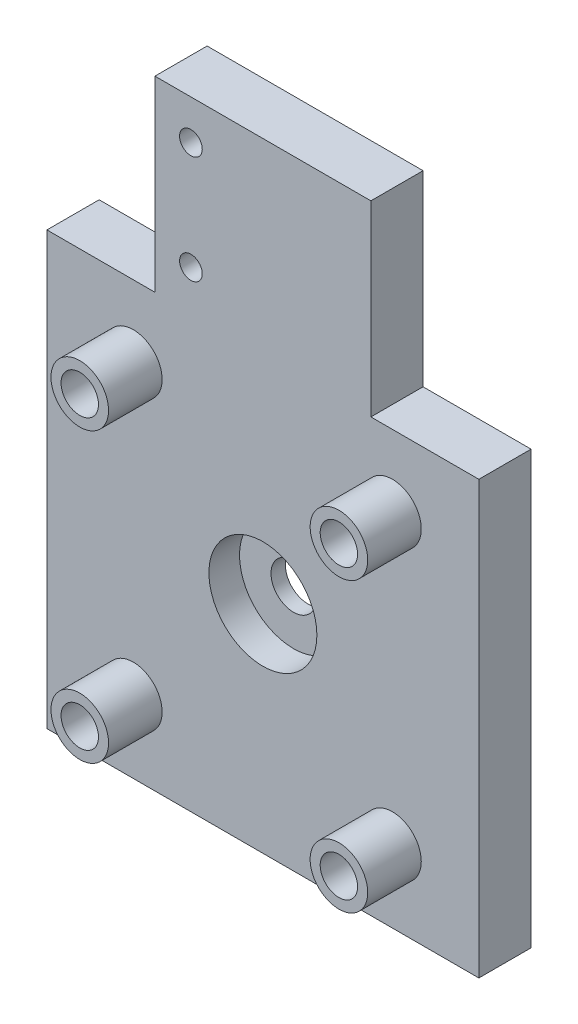
SolidWorks part; units mm, degrees
ref_plane "Front Plane" through (0, 0, 0) normal (0, 0, 1) x (1, 0, 0)
ref_plane "Top Plane" through (0, 0, 0) normal (0, 1, 0) x (1, 0, 0)
ref_plane "Right Plane" through (0, 0, 0) normal (1, 0, 0) x (0, 0, -1)
sketch "Sketch1" plane through (0, 0, 0) normal (0, 0, 1) x (1, 0, 0)
  line L1 (-19.05, -38.1) -> (19.05, -38.1)
  line L2 (-19.05, -38.1) -> (-19.05, 38.1)
  line L3 (-19.05, 38.1) -> (19.05, 38.1)
  line L4 (19.05, -38.1) -> (19.05, 38.1)
  line L5 (-19.05, -38.1) -> (19.05, 38.1) construction
  line L6 (-19.05, 38.1) -> (19.05, -38.1) construction
  point P0 (0, 0)
  dimension "D1" = 38.1
  dimension "D2" = 76.2
extrude "Boss-Extrude1" add sketch "Sketch1" along normal blind 7.9375
sketch "Sketch2" plane through (0, 0, 7.9375) normal (0, 0, 1) x (1, 0, 0)
  circle A0 centre (0, 0) radius 3.9688
  dimension "D1" = 7.9375
extrude "Cut-Extrude1" cut sketch "Sketch2" against normal through all
sketch "Sketch4" plane through (0, 0, 7.9375) normal (0, 0, 1) x (1, 0, 0)
  circle A0 centre (0, 0) radius 9.525
  dimension "D1" = 19.05
extrude "Cut-Extrude2" cut sketch "Sketch4" against normal offset from surface (5.3975 mm away) 2.54 up to face at (3.9688, 0, 0)
sketch "Sketch8" plane through (0, 0, 7.9375) normal (0, 0, 1) x (1, 0, 0)
  line L0 (19.05, 38.1) -> (-19.05, 38.1) construction
  line L1 (-19.05, 38.1) -> (-38.1, 38.1)
  line L2 (-19.05, 38.1) -> (-19.05, -38.1)
  line L3 (-19.05, -38.1) -> (-38.1, -38.1)
  line L4 (-38.1, 38.1) -> (-38.1, -38.1)
  line L5 (-19.05, 38.1) -> (-19.05, -38.1) construction
  line L6 (-19.05, -38.1) -> (19.05, -38.1) construction
  line L7 (0, 38.1) -> (0, -38.1) construction
  line L8 (19.05, -38.1) -> (38.1, -38.1)
  line L9 (38.1, 38.1) -> (38.1, -38.1)
  line L10 (19.05, 38.1) -> (38.1, 38.1)
  line L11 (19.05, 38.1) -> (19.05, -38.1)
  dimension "D1" = 38.1
extrude "Boss-Extrude5" add sketch "Sketch8" against normal up to surface (7.9375 mm away) up to face at (3.9688, 0, 0)
sketch "Sketch5" plane through (0, 0, 7.9375) normal (0, 0, 1) x (1, 0, 0)
  line L0 (38.1, 38.1) -> (-38.1, 38.1) construction
  line L1 (0, 38.1) -> (0, -38.1) construction
  line L2 (38.1, 38.1) -> (-38.1, 38.1) construction
  line L3 (-38.1, -38.1) -> (38.1, -38.1) construction
  circle A0 centre (22.86, 25.4) radius 5.08
  circle A1 centre (-22.86, 25.4) radius 5.08
  dimension "D1" = 10.16
  dimension "D2" = 12.7
  dimension "D3" = 22.86
extrude "Boss-Extrude2" add sketch "Sketch5" along normal blind 9.4488
sketch "Sketch6" plane through (0, 0, 17.3863) normal (0, 0, 1) x (1, 0, 0)
  line L0 (0, 38.1) -> (0, -38.1) construction
  line L1 (38.1, 38.1) -> (-38.1, 38.1) construction
  line L2 (-38.1, -38.1) -> (38.1, -38.1) construction
  circle A0 centre (22.86, 25.4) radius 3.302
  circle A1 centre (-22.86, 25.4) radius 3.302
  dimension "D1" = 6.604
extrude "Cut-Extrude3" cut sketch "Sketch6" against normal through all
mirror "Mirror1" about plane through (0, 0, 0) normal (0, 1, 0) of "Cut-Extrude3", "Boss-Extrude2"
sketch "Sketch7" plane through (0, 0, 7.9375) normal (0, 0, 1) x (1, 0, 0)
  line L0 (0, 71.12) -> (0, -38.1) construction
  line L1 (-19.05, 38.1) -> (19.05, 38.1)
  line L2 (-19.05, 38.1) -> (-19.05, 71.12)
  line L3 (-19.05, 71.12) -> (19.05, 71.12)
  line L4 (19.05, 38.1) -> (19.05, 71.12)
  line L6 (-19.05, 54.61) -> (19.05, 54.61) construction
  line L7 (-12.7, 71.12) -> (-12.7, 38.1) construction
  line L8 (-38.1, -38.1) -> (38.1, -38.1) construction
  line L9 (38.1, 38.1) -> (-38.1, 38.1) construction
  circle A0 centre (-12.7, 64.135) radius 2
  circle A1 centre (-12.7, 45.085) radius 2
  dimension "D3" = 4
  dimension "D1" = 33.02
  dimension "D2" = 6.35
  dimension "D4" = 9.525
  dimension "D5" = 38.1
extrude "Boss-Extrude4" add sketch "Sketch7" against normal up to surface (7.9375 mm away) up to face at (26.162, -25.4, 0)
sketch "Sketch9" plane through (0, 0, 0) normal (0, 0, -1) x (-1, 0, 0)
  line L1 (-12.7, -12.7) -> (12.7, -12.7)
  line L2 (-12.7, -12.7) -> (-12.7, 12.7)
  line L3 (-12.7, 12.7) -> (12.7, 12.7)
  line L4 (12.7, -12.7) -> (12.7, 12.7)
  line L5 (-12.7, -12.7) -> (12.7, 12.7) construction
  line L6 (-12.7, 12.7) -> (12.7, -12.7) construction
  line L22 (-19.05, 38.1) -> (-38.1, 38.1)
  line L23 (-38.1, 38.1) -> (-38.1, -38.1)
  line L24 (-38.1, -38.1) -> (38.1, -38.1)
  line L25 (38.1, -38.1) -> (38.1, 38.1)
  line L26 (38.1, 38.1) -> (19.05, 38.1)
  line L27 (19.05, 38.1) -> (19.05, 71.12)
  line L28 (19.05, 71.12) -> (-19.05, 71.12)
  line L29 (-19.05, 71.12) -> (-19.05, 38.1)
  line L30 (-19.05, 38.1) -> (-38.1, 38.1)
  line L31 (-38.1, 38.1) -> (-38.1, -38.1)
  line L32 (-38.1, -38.1) -> (38.1, -38.1)
  line L33 (38.1, -38.1) -> (38.1, 38.1)
  line L34 (38.1, 38.1) -> (19.05, 38.1)
  line L35 (19.05, 38.1) -> (19.05, 71.12)
  line L36 (19.05, 71.12) -> (-19.05, 71.12)
  line L37 (-19.05, 71.12) -> (-19.05, 38.1)
  circle A0 centre (-22.86, -25.4) radius 3.302 construction
  circle A1 centre (22.86, -25.4) radius 3.302 construction
  circle A2 centre (22.86, 25.4) radius 3.302 construction
  circle A3 centre (12.7, 64.135) radius 2 construction
  circle A4 centre (12.7, 45.085) radius 2 construction
  circle A5 centre (-22.86, 25.4) radius 3.302 construction
  circle A6 centre (-22.86, -25.4) radius 3.302
  circle A7 centre (22.86, -25.4) radius 3.302
  circle A8 centre (22.86, 25.4) radius 3.302
  circle A9 centre (12.7, 64.135) radius 2
  circle A10 centre (12.7, 45.085) radius 2
  circle A11 centre (-22.86, 25.4) radius 3.302
  point P0 (0, 0)
  dimension "D1" = 25.4
  dimension "D2" = 25.4
  dimension "D3" = 0
extrude "Boss-Extrude6" add sketch "Sketch9" along normal blind 1.27 contours L30 L31 L32 L33 L34 L35 L36 L37 | A11 | L2 L1 L4 L3 | A8 | A10 | A9 | A7 | A6
